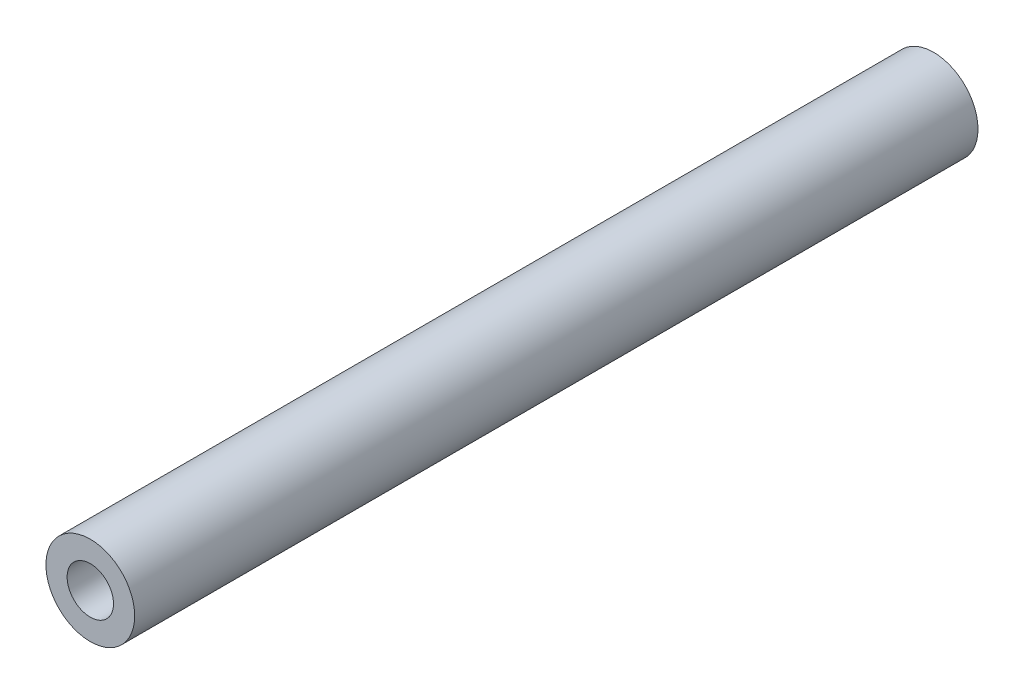
SolidWorks part; units mm, degrees
ref_plane "Front Plane" through (0, 0, 0) normal (0, 0, 1) x (1, 0, 0)
ref_plane "Top Plane" through (0, 0, 0) normal (0, 1, 0) x (1, 0, 0)
ref_plane "Right Plane" through (0, 0, 0) normal (1, 0, 0) x (0, 0, -1)
sketch "Sketch1" plane through (0, 0, 0) normal (0, 0, 1) x (1, 0, 0)
  circle A0 centre (0, 0) radius 2.4892
  circle A1 centre (0, 0) radius 4.7625
  dimension "D1" = 9.525
  dimension "D2" = 4.9784
extrude "Boss-Extrude1" add sketch "Sketch1" along normal blind 90.4875
